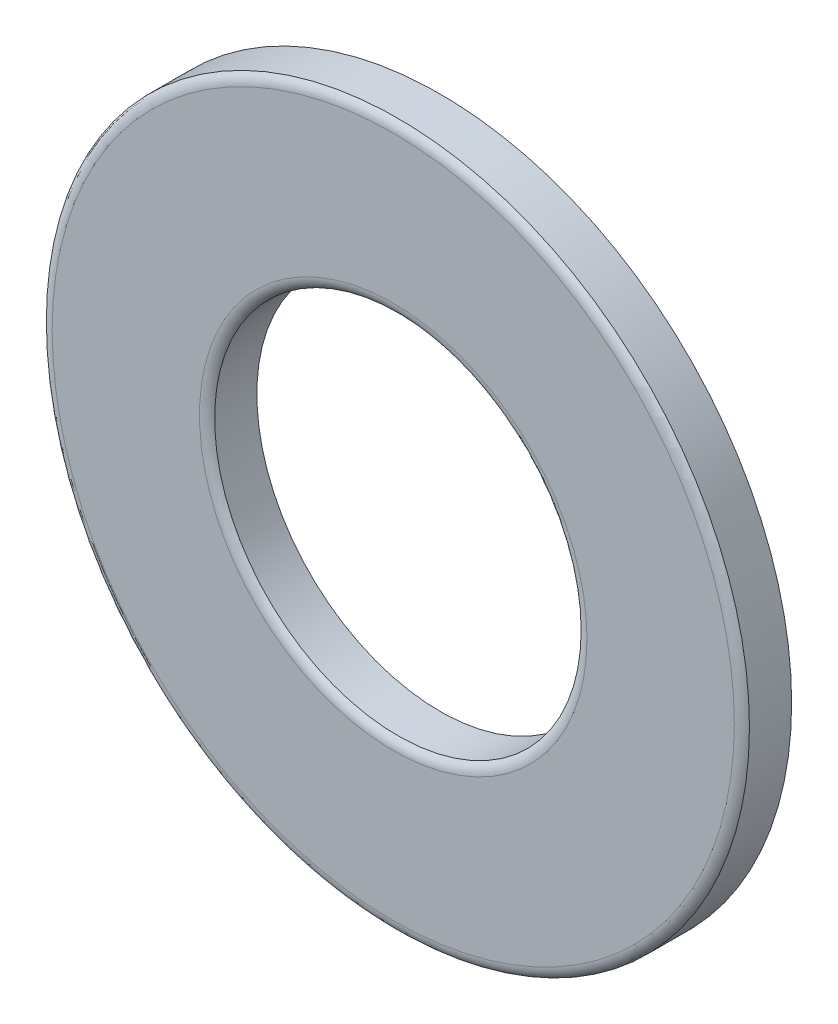
SolidWorks part; units mm, degrees
ref_plane "Front Plane" through (0, 0, 0) normal (0, 0, 1) x (1, 0, 0)
ref_plane "Top Plane" through (0, 0, 0) normal (0, 1, 0) x (1, 0, 0)
ref_plane "Right Plane" through (0, 0, 0) normal (1, 0, 0) x (0, 0, -1)
sketch "Sketch1" plane through (0, 0, 0) normal (0, 0, 1) x (1, 0, 0)
  circle A0 centre (0, 0) radius 9.525
  circle A1 centre (0, 0) radius 4.9657
  point P4 (4.9657, 0)
  dimension "ID" = 9.9314
  dimension "OD" = 19.05
sketch "Sketch2" plane through (0, 0, 0) normal (1, 0, 0) x (0, 0, -1)
  line L0 (-0.635, 9.525) -> (0.635, 9.525)
  line L1 (0, 9.525) -> (0, 8.255) construction
  point P2 (-0.7239, 9.525)
  point P3 (0, 9.525)
  point P4 (0.7239, 9.525)
  point P8 (-0.5461, 9.525)
  point P13 (0.5461, 9.525)
  dimension "Thickness Range" = 1.27
  dimension "Thickness Range Max" = 1.4478
  dimension "Thickness Range Min" = 1.0922
sketch "Sketch3" plane through (0, 0, 0) normal (0, 0, 1) x (1, 0, 0)
  circle A0 centre (0, 0) radius 4.9657 construction
  circle A1 centre (0, 0) radius 9.525 construction
  circle A2 centre (0, 0) radius 4.9657
  circle A3 centre (0, 0) radius 9.525
extrude "Boss-Extrude1" add sketch "Sketch3" along normal up to vertex (0.635 mm away) from vertex at -0.635 starting at point (0, 9.525, -0.635)
chamfer "Chamfer1" distance 0.127 angle 30 2 edges at (9.525, 0, 0.635) (4.9657, 0, 0.635)
fillet "Fillet1" radius 0.381 2 edges at (5.039, 0, 0.635) (9.4517, 0, 0.635)
equation "\"D1@Fillet1\"=\"D1@Chamfer1\"*3"
equation "\"D1@Chamfer1\"=\"Thickness Range@Sketch2\"*.1"
